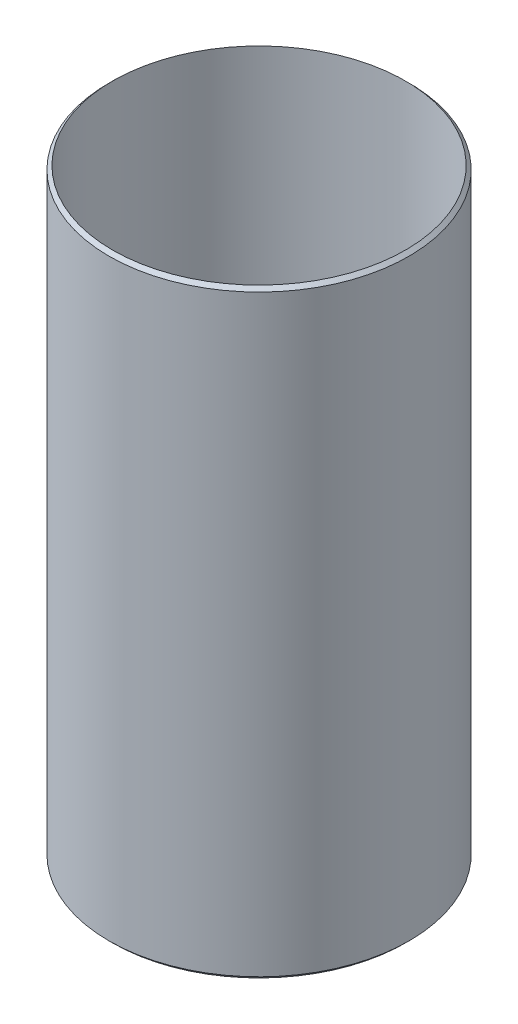
SolidWorks part; units mm, degrees
material "Plain Carbon Steel"
ref_plane "Front Plane" through (0, 0, 0) normal (0, 0, 1) x (1, 0, 0)
ref_plane "Top Plane" through (0, 0, 0) normal (0, 1, 0) x (1, 0, 0)
ref_plane "Right Plane" through (0, 0, 0) normal (1, 0, 0) x (0, 0, -1)
sketch "Sketch1" plane through (0, 0, 0) normal (0, 1, 0) x (1, 0, 0)
  circle A0 centre (0, 0) radius 83
  circle A1 centre (0, 0) radius 85
  dimension "D1" = 170
  dimension "D2" = 2
extrude "Boss-Extrude1" add sketch "Sketch1" along normal blind 340
chamfer "Chamfer1" distance 2 angle 45 2 edges at (0, 0, 85) (0, 340, 85)
equation "\"TubeDiameter\"= 6.6929in"
